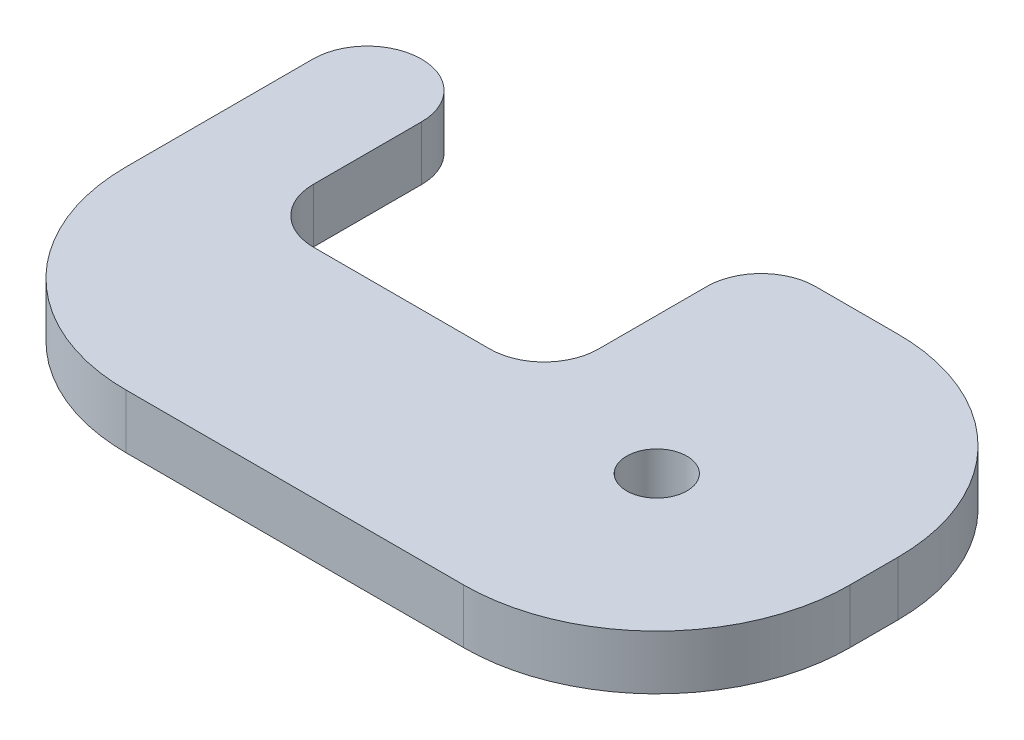
SolidWorks part; units mm, degrees
ref_plane "Front Plane" through (0, 0, 0) normal (0, 0, 1) x (1, 0, 0)
ref_plane "Top Plane" through (0, 0, 0) normal (0, 1, 0) x (1, 0, 0)
ref_plane "Right Plane" through (0, 0, 0) normal (1, 0, 0) x (0, 0, -1)
sketch "Sketch1" plane through (0, 0, 0) normal (0, 1, 0) x (1, 0, 0)
  line L1 (-19.05, 11.43) -> (19.05, 11.43)
  line L2 (-19.05, 11.43) -> (-19.05, -11.43)
  line L3 (-19.05, -11.43) -> (19.05, -11.43)
  line L4 (19.05, 11.43) -> (19.05, -11.43)
  dimension "D1" = 22.86
  dimension "D2" = 38.1
  dimension "D3" = 11.43
  dimension "D4" = 19.05
extrude "Boss-Extrude1" add sketch "Sketch1" along normal blind 3.175
fillet "Fillet1" radius 10.16 2 edges at (-19.05, 1.5875, 11.43) (19.05, 1.5875, 11.43)
sketch "Sketch3" plane through (0, 3.175, 0) normal (0, 1, 0) x (1, 0, 0)
  line L0 (-7.7526, -1.27) -> (18.5521, -1.27) construction
  circle A0 centre (8.89, -1.27) radius 1.5875
  arc A2 (8.89, -11.43) -> (19.05, -1.27) centre (8.89, -1.27) ccw construction
  circle A3 centre (-8.272, -1.27) radius 1.5875
  dimension "D1" = 3.175
  dimension "D6" = 3.175
  dimension "D5" = 17.162
extrude "Cut-Extrude1" cut sketch "Sketch3" against normal through all contours A0 L0 | L0 A0 region at (8.89, 3.175, 0.5962) region at (8.89, 3.175, 1.9438)
fillet "Fillet3" radius 10.16 1 edges at (19.05, 1.5875, -11.43)
scale "Scale1" scale about centroid uniform scaling no x scale factor 1.11 y scale factor 1 z scale factor 1.11
sketch "Sketch4" plane through (0, 3.175, 0) normal (0, 1, 0) x (1, 0, 0)
  line L0 (1.928, 9.4829) -> (1.928, -9.5417) construction
  line L1 (-14.7344, -0.0167) -> (1.928, -0.0167)
  line L2 (-14.7344, -0.0167) -> (-14.7344, 12.6579)
  line L3 (-14.7344, 12.6579) -> (1.928, 12.6579)
  line L4 (1.928, -0.0167) -> (1.928, 12.6579)
  line L5 (9.929, 12.6579) -> (-21.0844, 12.6579) construction
  line L7 (-9.8068, -12.7167) -> (9.929, -12.7167) construction
  line L9 (-21.0844, 12.6579) -> (-21.0844, -1.4391) construction
  dimension "D2" = 12.7
  dimension "D3" = 6.35
extrude "Cut-Extrude2" cut sketch "Sketch4" against normal through all contours L3 L4 L1 L2
fillet "Fillet7" radius 3.175 5 edges at (-14.7344, 1.5875, 0.0167) (1.928, 1.5875, 0.0167) (1.928, 1.5875, -12.6579) (-14.7344, 1.5875, -12.6579) (-21.0844, 1.5875, -12.6579)
equation "\"D4@Sketch1\"=\"D2@Sketch1\"/2"
equation "\"D3@Sketch1\"=\"D1@Sketch1\"/2"
